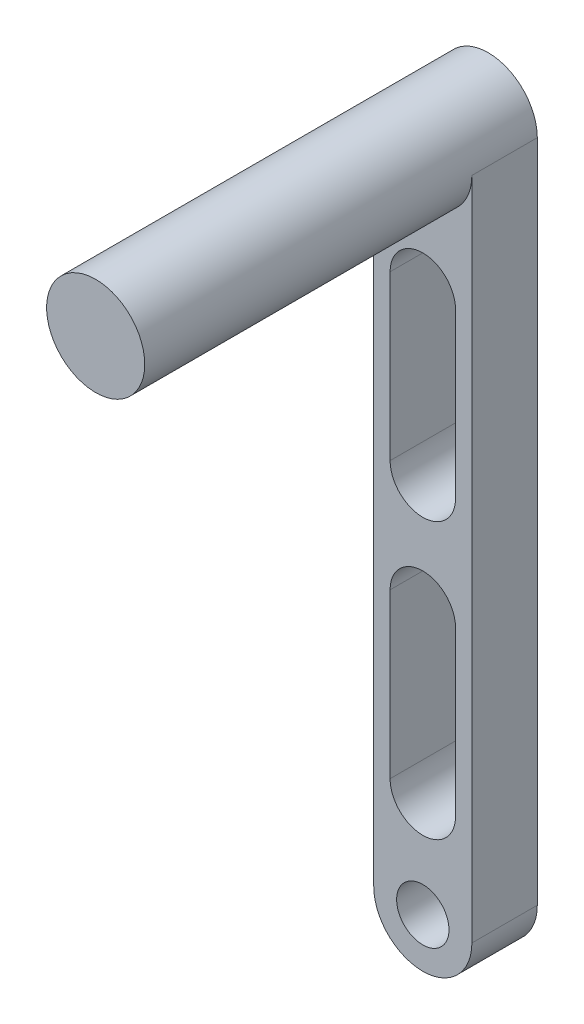
SolidWorks part; units mm, degrees
material "PEI"
ref_plane "Front Plane" through (0, 0, 0) normal (0, 0, 1) x (1, 0, 0)
ref_plane "Top Plane" through (0, 0, 0) normal (0, 1, 0) x (1, 0, 0)
ref_plane "Right Plane" through (0, 0, 0) normal (1, 0, 0) x (0, 0, -1)
sketch "Sketch1" plane through (0, 0, 0) normal (0, 0, 1) x (1, 0, 0)
  line L0 (0, -50.8) -> (0, 50.8) construction
  line L1 (-7.5, -50.8) -> (-7.5, 50.8)
  line L2 (7.5, -50.8) -> (7.5, 50.8)
  line L3 (0, -35.3) -> (0, -10.3) construction
  line L4 (-5, -35.3) -> (-5, -10.3)
  line L5 (5, -35.3) -> (5, -10.3)
  line L6 (0, 31.8) -> (0, 6.8) construction
  line L7 (5, 31.8) -> (5, 6.8)
  line L8 (-5, 31.8) -> (-5, 6.8)
  line L9 (-5, 19.3) -> (5, 19.3) construction
  line L10 (-5, -22.8) -> (5, -22.8) construction
  line L12 (0, 58.3) -> (0, 36.8) construction
  arc A0 (-7.5, -50.8) -> (7.5, -50.8) centre (0, -50.8) ccw
  arc A1 (7.5, 50.8) -> (-7.5, 50.8) centre (0, 50.8) ccw
  circle A2 centre (0, -50.8) radius 4
  arc A4 (-5, -35.3) -> (5, -35.3) centre (0, -35.3) ccw
  arc A5 (5, -10.3) -> (-5, -10.3) centre (0, -10.3) ccw
  arc A6 (5, 31.8) -> (-5, 31.8) centre (0, 31.8) ccw
  arc A7 (-5, 6.8) -> (5, 6.8) centre (0, 6.8) ccw
  circle A8 centre (0, 50.8) radius 7.5
  point P2 (0, 0)
  point P14 (0, -22.8)
  point P19 (0, 19.3)
  point P30 (0, -5.3)
  point P32 (0, -46.8)
  point P33 (0, -40.3)
  point P35 (0, 1.8)
  point P36 (0, 0)
  point P37 (0, 43.3)
  point P38 (0, 0)
  dimension "D3" = 8
  dimension "D1" = 101.6
  dimension "D2" = 15
  dimension "D4" = 10
  dimension "D5" = 6.5
  dimension "20" = 25
  dimension "D6" = 6.5
extrude "Boss-Extrude1" add sketch "Sketch1" along normal blind 10 contours A8 L1 A0 L2 A7 L8 A6 L7 A5 L5 A4 L4 A2 region at (-6.3987, 0, 0)
extrude "Boss-Extrude2" add sketch "Sketch1<4>" along normal blind 60 contours A1 A8 region at (0, 50.8, 0)
sketch "Sketch1<4>" plane through (0, 0, 0) normal (0, 0, 1) x (1, 0, 0) same geometry as "Sketch1"
